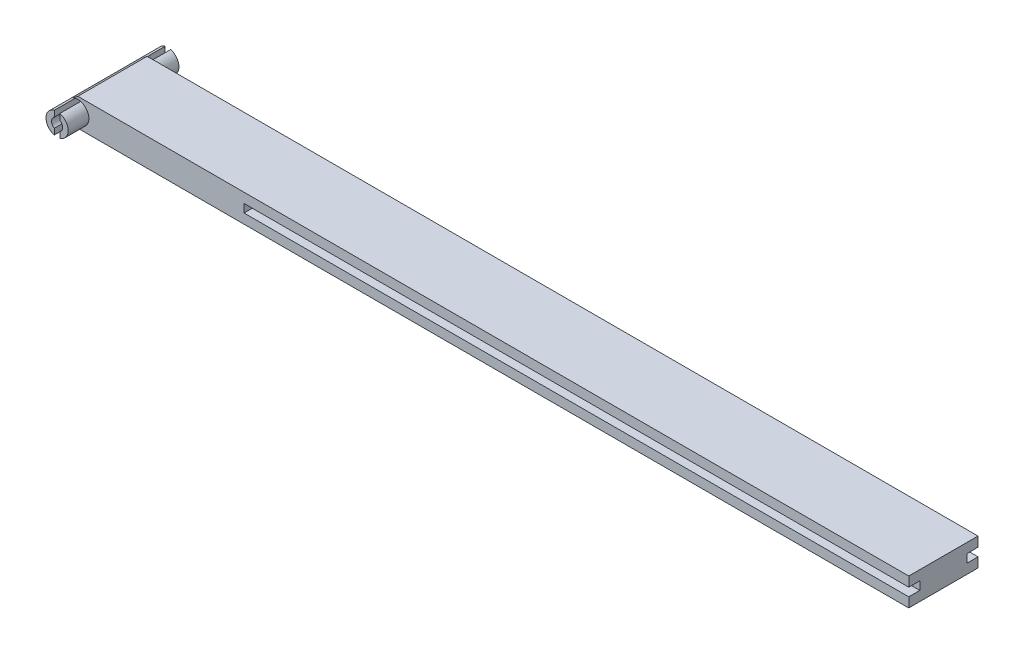
SolidWorks part; units mm, degrees
ref_plane "Front Plane" through (0, 0, 0) normal (0, 0, 1) x (1, 0, 0)
ref_plane "Top Plane" through (0, 0, 0) normal (0, 1, 0) x (1, 0, 0)
ref_plane "Right Plane" through (0, 0, 0) normal (1, 0, 0) x (0, 0, -1)
sketch "Sketch2" plane through (0, 0, 0) normal (0, 1, 0) x (1, 0, 0)
  line L0 (-75, 6.25) -> (75, -6.25) construction
  line L1 (-75, 6.25) -> (75, 6.25)
  line L2 (-75, 6.25) -> (-75, -6.25)
  line L3 (-75, -6.25) -> (75, -6.25)
  line L4 (75, 6.25) -> (75, -6.25)
  point P4 (0, 0)
  dimension "D1" = 12.5
  dimension "D2" = 150
extrude "Boss-Extrude1" add sketch "Sketch2" along normal blind 5
sketch "Sketch3" plane through (0, 0, 0) normal (0, 0, 1) x (1, 0, 0)
  line L0 (-75, 5) -> (-75, 0) construction
  circle A0 centre (-75, 2.5) radius 2
  dimension "D1" = 4
extrude "Boss-Extrude2" add sketch "Sketch3" along normal blind 10 and the other way blind 10
sketch "Sketch4" plane through (0, 0, 10) normal (0, 0, 1) x (1, 0, 0)
  circle A0 centre (-75, 2.5) radius 1
  dimension "D1" = 2
fillet "Fillet1" radius 10 2 edges at (-75, 4.5, 0) (-75, 0.5, 0)
extrude "Cut-Extrude1" cut sketch "Sketch4" against normal through all
sketch "Sketch5" plane through (0, 0, 10) normal (0, 0, 1) x (1, 0, 0)
  line L1 (-75.5, 4.5) -> (-74.5, 4.5)
  line L2 (-75.5, 4.5) -> (-75.5, 0.5)
  line L3 (-75.5, 0.5) -> (-74.5, 0.5)
  line L4 (-74.5, 4.5) -> (-74.5, 0.5)
  circle A1 centre (-75, 2.5) radius 2 construction
  point P8 (-75, 4.5)
  dimension "D1" = 1
extrude "Cut-Extrude2" cut sketch "Sketch5" against normal up to surface (16.25 mm away)
mirror "Mirror3" about plane through (0, 0, 0) normal (0, 0, 1) of "Cut-Extrude2"
sketch "Sketch6" plane through (0, 0, 6.25) normal (0, 0, 1) x (1, 0, 0)
  line L0 (75, 5) -> (75, 0) construction
  line L1 (75, 3.25) -> (-45, 3.25)
  line L2 (75, 3.25) -> (75, 1.75)
  line L3 (75, 1.75) -> (-45, 1.75)
  line L4 (-45, 3.25) -> (-45, 1.75)
  point P7 (75, 2.5)
  dimension "D1" = 1.5
  dimension "D2" = 120
extrude "Cut-Extrude3" cut sketch "Sketch6" against normal blind 2
mirror "Mirror4" about plane through (0, 0, 0) normal (0, 0, 1) of "Cut-Extrude3"
